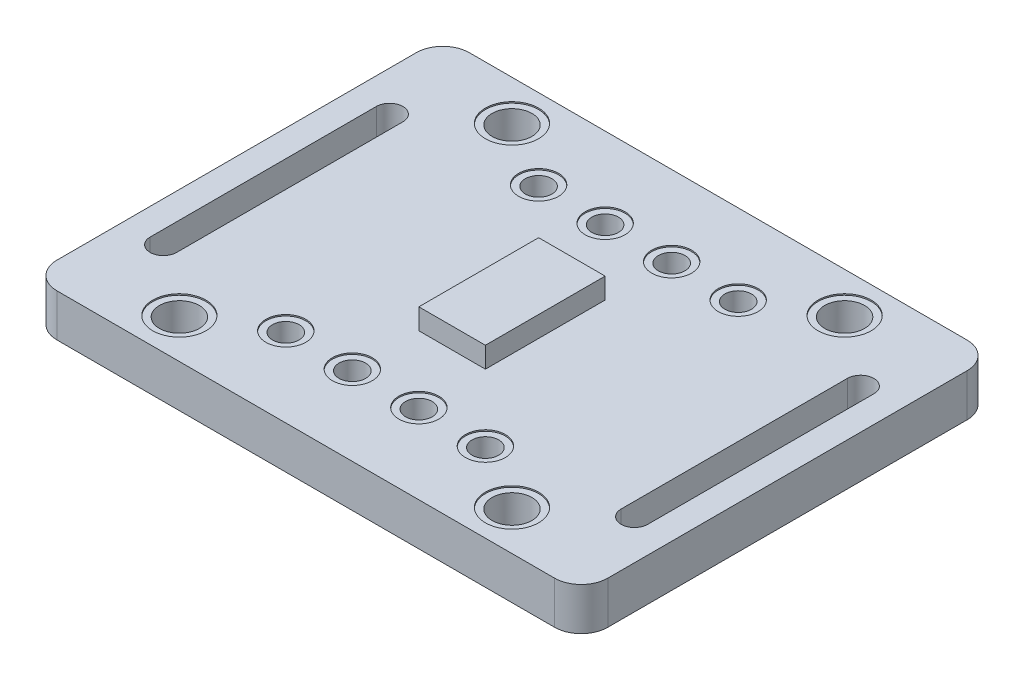
SolidWorks part; units mm, degrees
ref_plane "Front Plane" through (0, 0, 0) normal (0, 0, 1) x (1, 0, 0)
ref_plane "Top Plane" through (0, 0, 0) normal (0, 1, 0) x (1, 0, 0)
ref_plane "Right Plane" through (0, 0, 0) normal (1, 0, 0) x (0, 0, -1)
sketch "Sketch1" plane through (0, 0, 0) normal (0, 1, 0) x (1, 0, 0)
  line L1 (-10.35, -7.75) -> (10.35, -7.75)
  line L2 (-10.35, -7.75) -> (-10.35, 7.75)
  line L3 (-10.35, 7.75) -> (10.35, 7.75)
  line L4 (10.35, -7.75) -> (10.35, 7.75)
  line L5 (-10.35, -7.75) -> (10.35, 7.75) construction
  line L6 (-10.35, 7.75) -> (10.35, -7.75) construction
  point P0 (0, 0)
  dimension "D1" = 20.7
  dimension "D2" = 15.5
extrude "Boss-Extrude1" add sketch "Sketch1" along normal blind 1.6
fillet "Fillet1" radius 1 4 edges at (-10.35, 0.8, -7.75) (-10.35, 0.8, 7.75) (10.35, 0.8, -7.75) (10.35, 0.8, 7.75)
sketch "Sketch2" plane through (0, 1.6, 0) normal (0, 1, 0) x (1, 0, 0)
  line L0 (0, 7.75) -> (0, -7.75) construction
  line L1 (9.35, 7.75) -> (-9.35, 7.75) construction
  line L2 (-9.35, -7.75) -> (9.35, -7.75) construction
  circle A0 centre (-6.25, -6.25) radius 0.75
  circle A2 centre (-3.75, -4.75) radius 0.5
  circle A3 centre (-1.25, -4.75) radius 0.5
  circle A6 centre (6.25, -6.25) radius 0.75
  circle A7 centre (3.75, -4.75) radius 0.5
  circle A8 centre (1.25, -4.75) radius 0.5
  circle A9 centre (-6.25, -6.25) radius 1
  circle A10 centre (-3.75, -4.75) radius 0.75
  circle A11 centre (-1.25, -4.75) radius 0.75
  circle A12 centre (1.25, -4.75) radius 0.75
  circle A13 centre (3.75, -4.75) radius 0.75
  circle A14 centre (6.25, -6.25) radius 1
  dimension "D1" = 1
  dimension "D3" = 1.5
  dimension "D2" = 3
  dimension "D4" = 1.25
  dimension "D5" = 2.5
  dimension "D6" = 2.5
  dimension "D7" = 1.5
  dimension "D8" = 0.25
extrude "Cut-Extrude1" cut sketch "Sketch2" against normal through all contours A0 | A2 | A3 | A8 | A7 | A6 region at (-6.25, 1.6, 6.25) region at (-3.75, 1.6, 4.75) region at (-1.25, 1.6, 4.75) region at (6.25, 1.6, 6.25) region at (3.75, 1.6, 4.75) region at (1.25, 1.6, 4.75)
extrude "Cut-Extrude3" cut sketch "Sketch2<3>" against normal blind 0.05
sketch "Sketch2<3>" plane through (0, 1.6, 0) normal (0, 1, 0) x (1, 0, 0) same geometry as "Sketch2"
mirror "Mirror1" about plane through (0, 0, 0) normal (0, 0, 1) of "Cut-Extrude3", "Cut-Extrude1"
sketch "Sketch3" plane through (0, 1.6, 0) normal (0, 1, 0) x (1, 0, 0)
  line L0 (-10.35, 0) -> (10.35, 0) construction
  line L1 (-10.35, 6.75) -> (-10.35, -6.75) construction
  line L2 (10.35, -6.75) -> (10.35, 6.75) construction
  line L3 (-8.85, -4.25) -> (-8.85, 4.25) construction
  line L4 (-9.35, -4.25) -> (-9.35, 4.25)
  line L5 (-8.35, -4.25) -> (-8.35, 4.25)
  line L6 (0, 7.75) -> (0, -7.75) construction
  line L7 (9.35, 7.75) -> (-9.35, 7.75) construction
  line L8 (-9.35, -7.75) -> (9.35, -7.75) construction
  arc A0 (-9.35, -4.25) -> (-8.35, -4.25) centre (-8.85, -4.25) ccw
  arc A1 (-8.35, 4.25) -> (-9.35, 4.25) centre (-8.85, 4.25) ccw
  point P8 (-8.85, 0)
  dimension "D1" = 1
  dimension "D2" = 8.5
  dimension "D3" = 1.5
extrude "Cut-Extrude2" cut sketch "Sketch3" against normal through all
mirror "Mirror2" about plane through (0, 0, 0) normal (1, 0, 0) of "Cut-Extrude2"
sketch "Sketch4" plane through (0, 1.6, 0) normal (0, 1, 0) x (1, 0, 0)
  line L1 (-1.25, -2.25) -> (1.25, -2.25)
  line L2 (-1.25, -2.25) -> (-1.25, 2.25)
  line L3 (-1.25, 2.25) -> (1.25, 2.25)
  line L4 (1.25, -2.25) -> (1.25, 2.25)
  line L5 (-1.25, -2.25) -> (1.25, 2.25) construction
  line L6 (-1.25, 2.25) -> (1.25, -2.25) construction
  point P0 (0, 0)
  dimension "D1" = 2.5
  dimension "D2" = 4.5
extrude "Boss-Extrude2" add sketch "Sketch4" along normal blind 0.78
